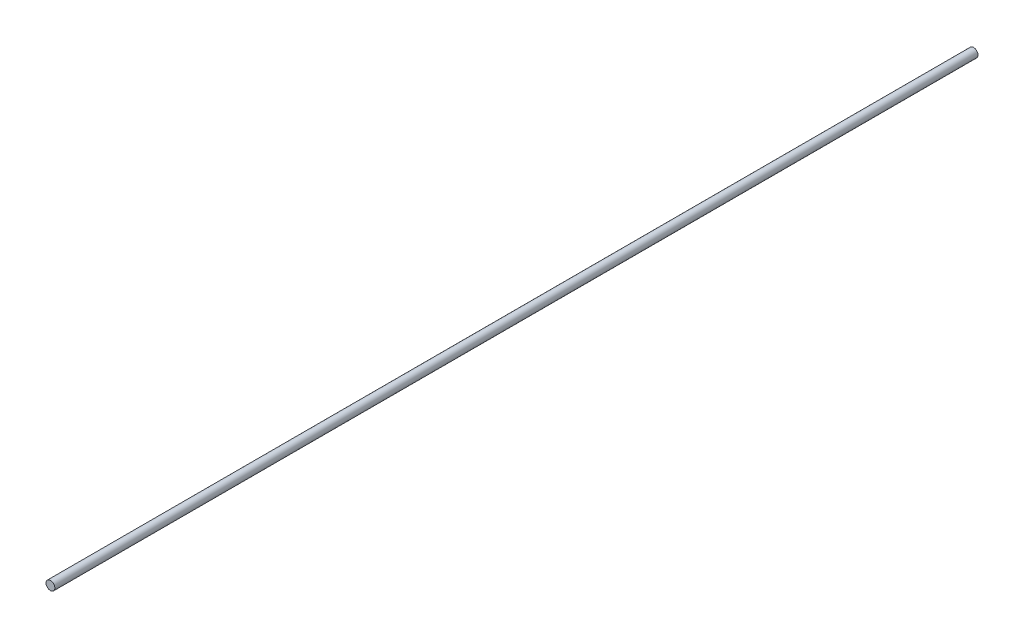
SolidWorks part; units mm, degrees
material "AISI 1020"
ref_plane "Front Plane" through (0, 0, 0) normal (0, 0, 1) x (1, 0, 0)
ref_plane "Top Plane" through (0, 0, 0) normal (0, 1, 0) x (1, 0, 0)
ref_plane "Right Plane" through (0, 0, 0) normal (1, 0, 0) x (0, 0, -1)
sketch "Sketch1" plane through (0, 0, 0) normal (0, 0, 1) x (1, 0, 0)
  circle A0 centre (0, 0) radius 7.9375
  dimension "D1" = 15.875
extrude "Boss-Extrude1" add sketch "Sketch1" along normal blind 2254.25
sketch "Sketch2" plane through (0, 0, 0) normal (0, 0, -1) x (-1, 0, 0)
  circle A0 centre (0, 0) radius 7.9375
extrude "Cut-Extrude1" cut sketch "Sketch2" against normal blind 596.9
